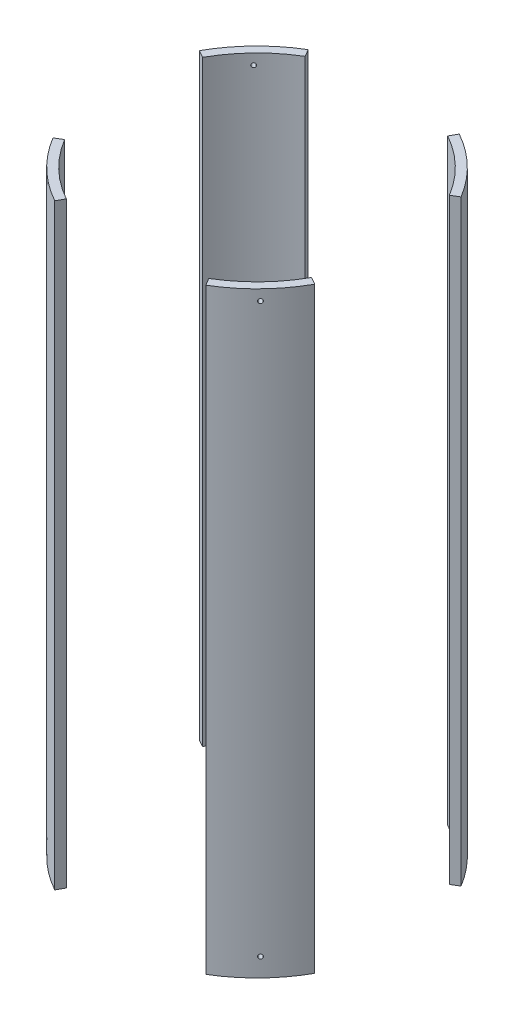
SolidWorks part; units mm, degrees
material "6061-T6 (SS)"
ref_plane "Front Plane" through (0, 0, 0) normal (0, 0, 1) x (1, 0, 0)
ref_plane "Top Plane" through (0, 0, 0) normal (0, 1, 0) x (1, 0, 0)
ref_plane "Right Plane" through (0, 0, 0) normal (1, 0, 0) x (0, 0, -1)
sketch "Sketch2" plane through (0, 0, 0) normal (0, 1, 0) x (1, 0, 0)
  circle A0 centre (0, 0) radius 88.9
  circle A1 centre (0, 0) radius 83.82
  dimension "D1" = 177.8
  dimension "D2" = 167.64
extrude "Boss-Extrude1" add sketch "Sketch2" along normal mid plane 356.743
sketch "Sketch3" plane through (0, 0, 0) normal (0, 1, 0) x (1, 0, 0)
  line L0 (0, 0) -> (169.6618, 101.6776)
  line L1 (-58.1167, 96.9749) -> (0, 0)
  line L2 (0, 0) -> (53.9, 96.9749)
  line L3 (53.9, 96.9749) -> (-58.1167, 96.9749)
  line L4 (0, 0) -> (70.9917, -118.4586)
  line L5 (70.9917, -118.4586) -> (-65.8409, -118.4586)
  line L6 (-65.8409, -118.4586) -> (0, 0)
  line L7 (169.6618, 101.6776) -> (169.6618, -94.3004)
  line L8 (169.6618, -94.3004) -> (0, 0)
  line L9 (0, 0) -> (-123.7413, 68.7771)
  line L10 (-123.7413, 68.7771) -> (-123.7413, -74.1577)
  line L11 (-123.7413, -74.1577) -> (0, 0)
  dimension "D1" = 60
  dimension "D2" = 60
  dimension "D3" = 60
  dimension "D4" = 60
  dimension "D5" = 30
  dimension "D6" = 30
extrude "Cut-Extrude1" cut sketch "Sketch3" against normal through all both and the other way through all contours L8 L7 L0 | L2 L3 L1 | L10 L11 L9 | L6 L5 L4 region at (-1.4056, 0, -64.65) region at (1.7169, 0, 78.9724) region at (113.1078, 0, -2.4591) region at (-82.4942, 0, 1.7935)
ref_plane "Bolt reference plane" through (-56.3092, 0, 58.1758) normal (0.6955, 0, -0.7185) x (-0.7185, 0, -0.6955)
sketch "Sketch5" plane through (-56.3092, 0, 58.1758) normal (0.6955, 0, -0.7185) x (-0.7185, 0, -0.6955)
  line L0 (-23.009, -178.3715) -> (23.009, -178.3715) construction
  circle A0 centre (-0.0228, 172.0215) radius 1.27
  circle A1 centre (-0.0228, -167.259) radius 1.27
  dimension "D1" = 2.54
  dimension "D4" = 11.1125
  dimension "D2" = 21.717
  dimension "D3" = 6.35
extrude "Bolt holes" cut sketch "Sketch5" against normal through all
pattern_circular "Bolt pattern" count 4 over 360 about axis through (0, 178.3715, 0) along (0, 1, 0) of "Bolt holes"
equation "\"D1@Boss-Extrude1\"=3*12"
